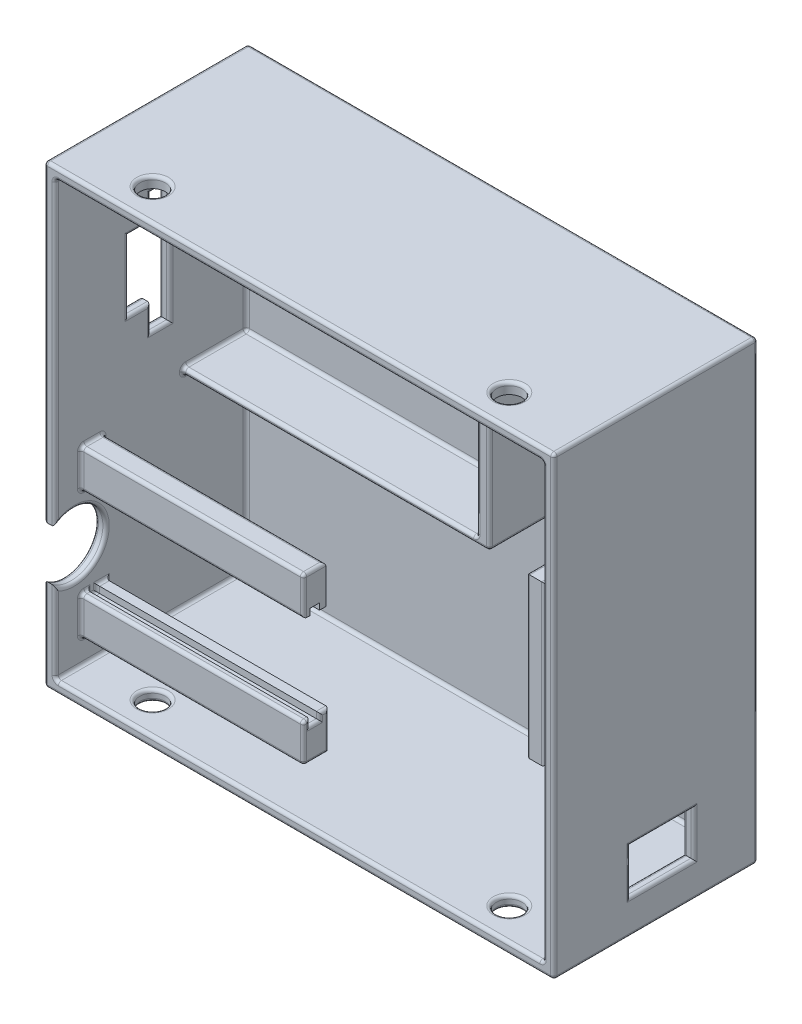
SolidWorks part; units mm, degrees
ref_plane "Plan de face" through (0, 0, 0) normal (0, 0, 1) x (1, 0, 0)
ref_plane "Plan de dessus" through (0, 0, 0) normal (0, 1, 0) x (1, 0, 0)
ref_plane "Plan de droite" through (0, 0, 0) normal (1, 0, 0) x (0, 0, -1)
sketch "Esquisse1" plane through (0, 0, 0) normal (0, 0, 1) x (1, 0, 0)
  line L1 (-40, 35.75) -> (40, 35.75)
  line L2 (-40, 35.75) -> (-40, -35.75)
  line L3 (-40, -35.75) -> (40, -35.75)
  line L4 (40, 35.75) -> (40, -35.75)
  line L5 (-40, 35.75) -> (40, -35.75) construction
  line L6 (-40, -35.75) -> (40, 35.75) construction
  point P0 (0, 0)
  dimension "D1" = 80
  dimension "D2" = 71.5
extrude "Boss.-Extru.1" add sketch "Esquisse1" along normal blind 2 contours L2 L3 L4 L1
sketch "Esquisse2" plane through (0, 0, 2) normal (0, 0, 1) x (1, 0, 0)
  line L0 (-40, 35.75) -> (40, 35.75)
  line L1 (40, 35.75) -> (40, -35.75) construction
  line L2 (-40, 35.75) -> (40, 35.75) construction
  line L3 (40, 35.75) -> (40, -35.75)
  line L4 (40, -35.75) -> (-40, -35.75)
  line L5 (-40, -35.75) -> (-40, 35.75)
  line L7 (-38.3, 34.05) -> (38.3, 34.05)
  line L8 (-38.3, 34.05) -> (-38.3, -34.05)
  line L9 (-38.3, -34.05) -> (38.3, -34.05)
  line L10 (38.3, 34.05) -> (38.3, -34.05)
  line L11 (-38.3, 34.05) -> (38.3, -34.05) construction
  line L12 (-38.3, -34.05) -> (38.3, 34.05) construction
  point P7 (0, 0)
  dimension "D1" = 1.7
  dimension "D2" = 1.7
extrude "Boss.-Extru.2" add sketch "Esquisse2" along normal blind 30
sketch "Esquisse3" plane through (0, 0, 2) normal (0, 0, 1) x (1, 0, 0)
  line L0 (-38.3, -2.45) -> (9.9, -2.45)
  line L1 (-38.3, 34.05) -> (-38.3, -34.05) construction
  line L2 (9.9, -2.45) -> (9.9, 34.05)
  line L3 (38.3, 34.05) -> (-38.3, 34.05) construction
  line L4 (-38.3, -2.45) -> (-38.3, -1.45)
  line L5 (-38.3, 34.05) -> (-38.3, -34.05) construction
  line L6 (-38.3, -1.45) -> (7.9, -1.45)
  line L7 (7.9, -1.45) -> (7.9, 34.05)
  line L8 (38.3, 34.05) -> (-38.3, 34.05) construction
  line L9 (7.9, 34.05) -> (9.9, 34.05)
  dimension "D1" = 1
  dimension "D2" = 2
  dimension "D3" = 46.2
  dimension "D4" = 35.5
extrude "Boss.-Extru.3" add sketch "Esquisse3" along normal blind 10 contours L6 L7 L9 L2 L0 L4
sketch "Esquisse4" plane through (0, 0, 2) normal (0, 0, 1) x (1, 0, 0)
  line L0 (15.7, -2.45) -> (15.7, -27.45)
  line L1 (15.7, -2.45) -> (18.5917, -2.45)
  line L2 (15.7, -27.45) -> (18.5917, -27.45)
  line L3 (18.5917, -2.45) -> (18.5917, -27.45)
  line L4 (-38.3, 34.05) -> (-38.3, -34.05) construction
  line L5 (-38.3, -2.45) -> (9.9, -2.45) construction
  dimension "D1" = 54
  dimension "D2" = 25
extrude "Boss.-Extru.4" add sketch "Esquisse4" along normal blind 10
sketch "Esquisse5" plane through (-40, 0, 0) normal (-1, 0, 0) x (0, 0, 1)
  line L0 (14, 24.75) -> (14, 5.75)
  line L1 (14, 5.75) -> (17, 5.75)
  line L2 (17, 5.75) -> (17, 9.75)
  line L3 (17, 9.75) -> (20.5, 9.75)
  line L4 (20.5, 9.75) -> (20.5, 20.75)
  line L5 (20.5, 20.75) -> (17, 20.75)
  line L6 (17, 20.75) -> (17, 24.75)
  line L7 (17, 24.75) -> (14, 24.75)
  line L8 (32, 35.75) -> (0, 35.75) construction
  line L9 (0, 35.75) -> (0, -35.75) construction
  point P3 (15.5, 24.75)
  dimension "D1" = 3
  dimension "D2" = 6.5
  dimension "D3" = 11
  dimension "D4" = 30
  dimension "D5" = 3
  dimension "D6" = 4
  dimension "D7" = 4
  dimension "D8" = 14
extrude "Enlèv. mat.-Extru.1" cut sketch "Esquisse5" against normal blind 10
sketch "Esquisse6" plane through (40, 0, 0) normal (1, 0, 0) x (0, 0, -1)
  line L0 (-20, -23.3322) -> (-20, -30.3322)
  line L1 (-20, -23.3322) -> (-10, -23.3322)
  line L2 (-20, -30.3322) -> (-10, -30.3322)
  line L3 (-10, -23.3322) -> (-10, -30.3322)
  line L4 (0, 35.75) -> (0, -35.75) construction
  dimension "D1" = 10
  dimension "D2" = 7
  dimension "D3" = 10
extrude "Enlèv. mat.-Extru.2" cut sketch "Esquisse6" against normal blind 10
sketch "Esquisse7" plane through (-38.3, 0, 0) normal (1, 0, 0) x (0, 0, -1)
  line L0 (-28, -10.25) -> (-28, -4.25)
  line L1 (-28, -4.25) -> (-24.5, -4.25)
  line L2 (-24.5, -4.25) -> (-24.5, -10.2589)
  line L3 (-24.5, -10.2589) -> (-25.5, -10.25)
  line L4 (-25.5, -10.25) -> (-25.5, -9.25)
  line L5 (-25.5, -9.25) -> (-27, -9.25)
  line L6 (-27, -9.25) -> (-27, -10.25)
  line L7 (-27, -10.25) -> (-28, -10.25)
  line L8 (0, 35.75) -> (0, -35.75) construction
  line L9 (-32, 35.75) -> (0, 35.75) construction
  line L10 (-28, -24.25) -> (-28, -30.25)
  line L11 (-28, -30.25) -> (-24, -30.25)
  line L12 (-24, -30.25) -> (-24, -24.25)
  line L13 (-24, -24.25) -> (-25.5, -24.25)
  line L14 (-25.5, -24.25) -> (-25.5, -25.25)
  line L15 (-25.5, -25.25) -> (-27, -25.25)
  line L16 (-27, -25.25) -> (-27, -24.25)
  line L17 (-27, -24.25) -> (-28, -24.25)
  point P10 (-26.25, -4.25)
  dimension "D1" = 24.5
  dimension "D2" = 1.5
  dimension "D3" = 1
  dimension "D4" = 14
  dimension "D5" = 5
  dimension "D6" = 1
  dimension "D7" = 1
  dimension "D8" = 40
  dimension "D9" = 16
  dimension "D10" = 1
  dimension "D11" = 14
  dimension "D12" = 6
  dimension "D13" = 4
  dimension "D14" = 1.5
  dimension "D15" = 16
  dimension "D16" = 6
  dimension "D17" = 1
  dimension "D18" = 1
extrude "Boss.-Extru.5" add sketch "Esquisse7" along normal blind 35
sketch "Esquisse8" plane through (-40, 0, 0) normal (-1, 0, 0) x (0, 0, 1)
  line L0 (28, -10.25) -> (28, -24.25) construction
  circle A0 centre (29, -17.25) radius 5
  point P7 (28, -17.25)
  dimension "D1" = 10
  dimension "D2" = 2
extrude "Enlèv. mat.-Extru.3" cut sketch "Esquisse8" against normal blind 35
sketch "Esquisse10" plane through (0, -35.75, 0) normal (0, -1, 0) x (1, 0, 0)
  line L0 (-3.3, 27) -> (-38.3, 27) construction
  line L2 (-40, 32) -> (-40, 0) construction
  circle A0 centre (-28, 27) radius 2
  dimension "D1" = 4
  dimension "D2" = 12
extrude "Enlèv. mat.-Extru.4" cut sketch "Esquisse10" against normal blind 5
mirror "Symétrie1" about plane through (0, 0, 0) normal (1, 0, 0) of "Enlèv. mat.-Extru.4"
mirror "Symétrie2" about plane through (0, 0, 0) normal (0, 1, 0) of "Symétrie1", "Enlèv. mat.-Extru.4"
fillet "Congé1" radius 0.5 115 edges at (9.9, 34.05, 7) (17.1458, -2.45, 2) (17.1458, -27.45, 2) (8.9, 34.05, 12) (9.9, 15.8, 2) (0, 34.05, 32) (18.5917, -27.45, 7) (18.5917, -14.95, 12) (18.5917, -2.45, 7) (18.5917, -14.95, 2) (15.7, -2.45, 7) (15.7, -14.95, 12) (15.7, -27.45, 7) (15.7, -14.95, 2) (7.9, 34.05, 7) (7.9, 16.3, 12) (7.9, 16.3, 2) (7.9, -1.45, 7) (-15.2, -1.45, 12) (-15.2, -1.45, 2) (-14.2, -2.45, 12) (9.9, -2.45, 7) (-14.2, -2.45, 2) (-3.3, -24.75, 27) (-3.3, -25.25, 26.25) (-3.3, -24.75, 25.5) (-3.3, -24.25, 24.75) (-3.3, -27.25, 24) (-3.3, -30.25, 26) (-3.3, -24.25, 27.5) (-20.8, -24.25, 28) (-3.3, -27.25, 28) (-20.8, -30.25, 28) (-20.8, -4.25, 24.5) (-3.3, -4.25, 26.25) (-20.8, -4.25, 28) (-3.3, -7.25, 28) (-20.8, -10.25, 28) (38.3, 34.05, 17) (38.3, 0, 32) (38.3, 0, 2) (38.3, -26.8322, 10) (38.3, -30.3322, 15) (38.3, -26.8322, 20) (38.3, -23.3322, 15) (38.3, -34.05, 17) (0, -34.05, 32) (0, -34.05, 2) (-28, -34.05, 29) (28, -34.05, 29) (-38.3, -30.25, 26) (-38.3, -27.25, 24) (-38.3, -24.25, 24.75) (-38.3, -24.75, 25.5) (-38.3, -25.25, 26.25) (-38.3, -24.75, 27) (-38.3, -24.25, 27.5) (-38.3, -27.25, 28) (-38.3, -9.25, 26.25) (-38.3, -9.75, 25.5) (-38.3, -10.2545, 25) (-38.3, -7.2545, 24.5) (-38.3, -4.25, 26.25) (-38.3, -7.25, 28) (-38.3, -10.25, 27.5) (-38.3, -9.75, 27) (-38.3, 22.75, 17) (-38.3, 20.75, 18.75) (-38.3, 15.25, 20.5) (-38.3, 9.75, 18.75) (-38.3, 7.75, 17) (-38.3, 5.75, 15.5) (-38.3, 15.25, 14) (-38.3, 24.75, 15.5) (-38.3, 10.4, 32) (-38.3, 34.05, 17) (-38.3, 16.3, 2) (-38.3, -1.45, 7) (-38.3, -1.95, 12) (-38.3, -2.45, 7) (-38.3, -18.25, 2) (-38.3, -34.05, 17) (-38.3, -27.65, 32) (-38.3, -17.25, 24) (40, 0, 32) (40, -26.8322, 20) (40, -30.3322, 15) (40, -26.8322, 10) (40, -23.3322, 15) (0, -35.75, 32) (40, -35.75, 16) (-28, -35.75, 25) (28, -35.75, 25) (-40, -35.75, 16) (-40, 11.25, 32) (-40, -17.25, 24) (-40, -28.5, 32) (-40, 5.75, 15.5) (-40, 7.75, 17) (-40, 9.75, 18.75) (-40, 15.25, 20.5) (-40, 20.75, 18.75) (-40, 22.75, 17) (-40, 24.75, 15.5) (-40, 15.25, 14) (40, 35.75, 16) (0, 35.75, 32) (-40, 35.75, 16) (-28, 35.75, 25) (28, 35.75, 25) (-40, 0, 0) (0, -35.75, 0) (40, 0, 0) (0, 35.75, 0) (9.9, 15.8, 12)
